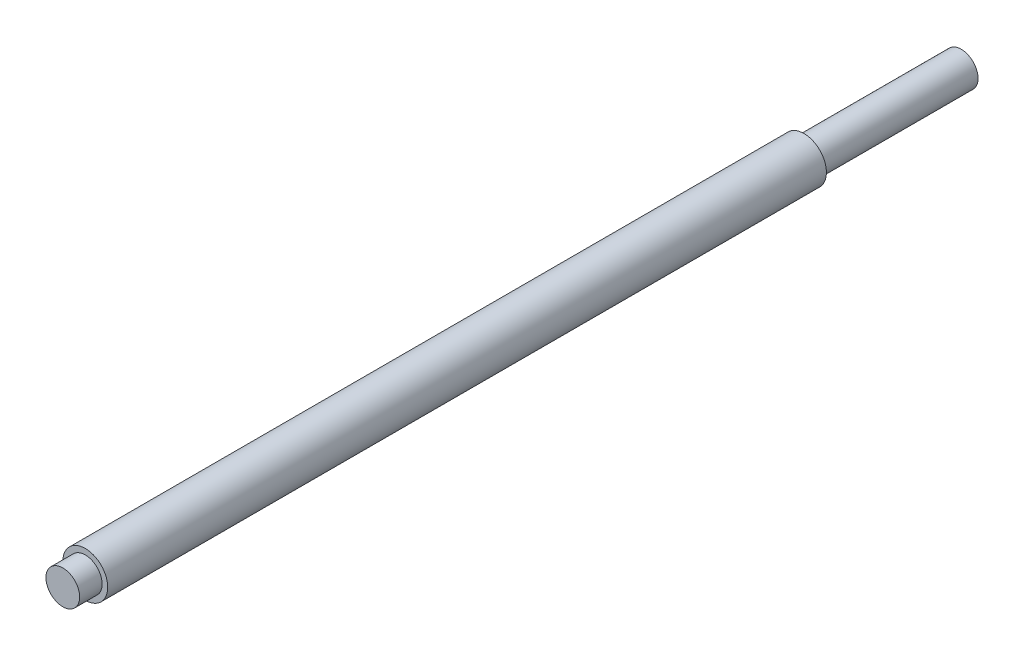
SolidWorks part; units mm, degrees
ref_plane "Front Plane" through (0, 0, 0) normal (0, 0, 1) x (1, 0, 0)
ref_plane "Top Plane" through (0, 0, 0) normal (0, 1, 0) x (1, 0, 0)
ref_plane "Right Plane" through (0, 0, 0) normal (1, 0, 0) x (0, 0, -1)
sketch "Sketch1" plane through (0, 0, 0) normal (0, 0, 1) x (1, 0, 0)
  circle A0 centre (0, 0) radius 6.35
  dimension "D1" = 12.7
extrude "Boss-Extrude1" add sketch "Sketch1" along normal blind 254 contours A0
sketch "Sketch2" plane through (0, 0, 0) normal (0, 0, -1) x (-1, 0, 0)
  circle A0 centre (0, 0) radius 6.35
  circle A1 centre (0, 0) radius 4.7625
  circle A2 centre (0, 0) radius 6.35 construction
  dimension "D1" = 9.525
extrude "long-trim" cut sketch "Sketch2" against normal blind 44.45
sketch "Sketch3" plane through (0, 0, 254) normal (0, 0, 1) x (1, 0, 0)
  circle A0 centre (0, 0) radius 6.35
  circle A1 centre (0, 0) radius 4.7625
  circle A2 centre (0, 0) radius 6.35 construction
  dimension "D1" = 9.525
extrude "Cut-Extrude2" cut sketch "Sketch3" against normal blind 6.35
sketch "Sketch4" plane through (0, 0, 44.45) normal (0, 0, -1) x (-1, 0, 0)
  circle A0 centre (0, 0) radius 5.08
curve "Helix/Spiral1" pitch 2.54 height 203.2 turns 80
sketch "Sketch5" plane through (0, 0, 0) normal (0, 1, 0) x (1, 0, 0)
  line L0 (6.35, -44.45) -> (5.08, -44.7784)
  line L1 (5.08, -44.7784) -> (5.08, -46.0484)
  line L2 (5.08, -46.0484) -> (6.35, -46.3769)
  line L3 (6.35, -46.3769) -> (6.35, -44.45)
  dimension "D1" = 29
  dimension "D2" = 1.27
  dimension "D3" = 1.27
sweep "Cut-Sweep1" [suppressed] cut profiles "Sketch5" path "Helix/Spiral1"
equation "\"dovetail-angle\" = 55"
equation "\"dovetail-stock-width\" = 5"
equation "\"dovetail-stock-height\" = 1.25"
equation "\"dovetail-depth\" = 0.5 * \"dovetail-stock-height\""
equation "\"dovetail-throat-width\" = \"dovetail-stock-width\" - (2 * \"dovetail-depth\")"
equation "\"delta-x\" = 6"
equation "\"delta-y\" = 3"
equation "\"delta-z\"= 2.5"
equation "\"gib-thickness\" = 0.25"
equation "\"x-slide-length\" = \"dovetail-stock-width\" + \"delta-x\""
equation "\"y-slide-length\" = \"dovetail-stock-width\" + \"delta-y\""
equation "\"dog-point-diam\" = .149"
equation "\"dog-point-length\" = .067"
equation "\"dovetail-double-height\" = 2 * \"dovetail-depth\" + 0.5"
equation "\"acme-major-diam\" = .5"
equation "\"acme-pitch-diam\" = 0.45"
equation "\"D1@Sketch1\"=\"acme-major-diam\""
equation "\"acme-minor-diam\" = 0.4"
equation "\"D1@Boss-Extrude1\"=\"y-screw-length\""
equation "\"acme-nut-od\" = 1.47"
equation "\"acme-nut-length\" = 1"
equation "\"acme-nut-trim-height\" = .75"
equation "\"screw-bearing-od\" = 0.5"
equation "\"screw-bearing-length\" = .25"
equation "\"screw-bearing-id\" = .375"
equation "\"end-plate-thickness\" = \"screw-bearing-length\""
equation "\"D1@Sketch2\"=\"screw-bearing-id\""
equation "\"screw-add-length\" = 2 * \"end-plate-thickness\" + 1 + 0.5"
equation "\"x-screw-length\" = \"x-slide-length\" + \"screw-add-length\""
equation "\"y-screw-length\" = \"y-slide-length\" + \"screw-add-length\""
equation "\"D1@long-trim\"=\"screw-add-length\"-\"end-plate-thickness\""
equation "\"D1@Sketch3\"=\"screw-bearing-id\""
equation "\"D1@Cut-Extrude2\"=\"end-plate-thickness\""
equation "\"acme-nut-mount-hole-space-horz\" = 0.82"
equation "\"acme-nut-mount-hole-space-vert\" = 0.5 * \"acme-nut-length\""
